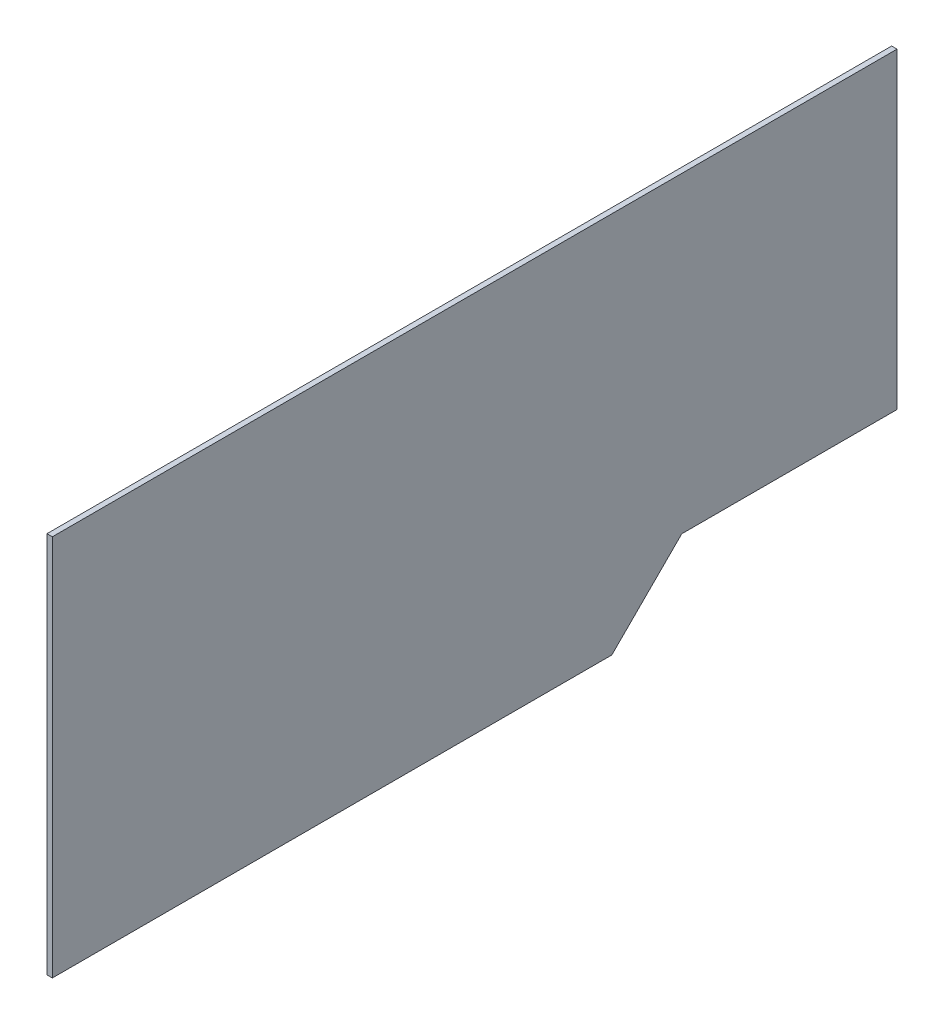
SolidWorks part; units mm, degrees
material "6061-T6 (SS)"
ref_plane "X-Y Datum" through (0, 0, 0) normal (0, 0, 1) x (1, 0, 0)
ref_plane "X-Z Datum" through (0, 0, 0) normal (0, 1, 0) x (1, 0, 0)
ref_plane "Y-Z Datum" through (0, 0, 0) normal (1, 0, 0) x (0, 0, -1)
sketch "Sketch1" plane through (0, 0, 0) normal (1, 0, 0) x (0, 0, -1)
  line L1 (-249.174, 88.9) -> (249.174, 88.9)
  line L2 (-249.174, 88.9) -> (-249.174, -88.9)
  line L3 (-249.174, -88.9) -> (249.174, -88.9)
  line L4 (249.174, 88.9) -> (249.174, -88.9)
  line L5 (-249.174, 88.9) -> (249.174, -88.9) construction
  line L6 (-249.174, -88.9) -> (249.174, 88.9) construction
  point P0 (0, 0)
  dimension "D1" = 177.8
  dimension "D2" = 498.348
extrude "Boss-Extrude1" add sketch "Sketch1" along normal mid plane 3.175
sketch "Sketch2" plane through (1.5875, 0, 0) normal (1, 0, 0) x (0, 0, -1)
  line L0 (249.174, -88.9) -> (249.174, -95.25)
  line L1 (249.174, -95.25) -> (122.174, -95.25)
  line L2 (122.174, -95.25) -> (80.899, -136.525)
  line L5 (-249.174, -88.9) -> (249.174, -88.9) construction
  line L6 (-249.174, -88.9) -> (249.174, -88.9)
  line L8 (80.899, -136.525) -> (-249.174, -136.525)
  line L9 (-249.174, -136.525) -> (-249.174, -88.9)
  line L10 (249.174, -88.9) -> (249.174, 88.9) construction
  line L11 (-249.174, 88.9) -> (-249.174, -88.9) construction
  point P5 (76.2331, -139.7)
  line M10 (-249.174, -88.9) -> (249.174, -88.9)
  dimension "D1" = 6.35
  dimension "D2" = 127
  dimension "D5" = 47.625
  dimension "D6" = 135
extrude "Boss-Extrude2" add sketch "Sketch2" against normal blind 3.175 contours L2 L1 L0 M10 region at (1.5875, -111.2835, 60.4101)
